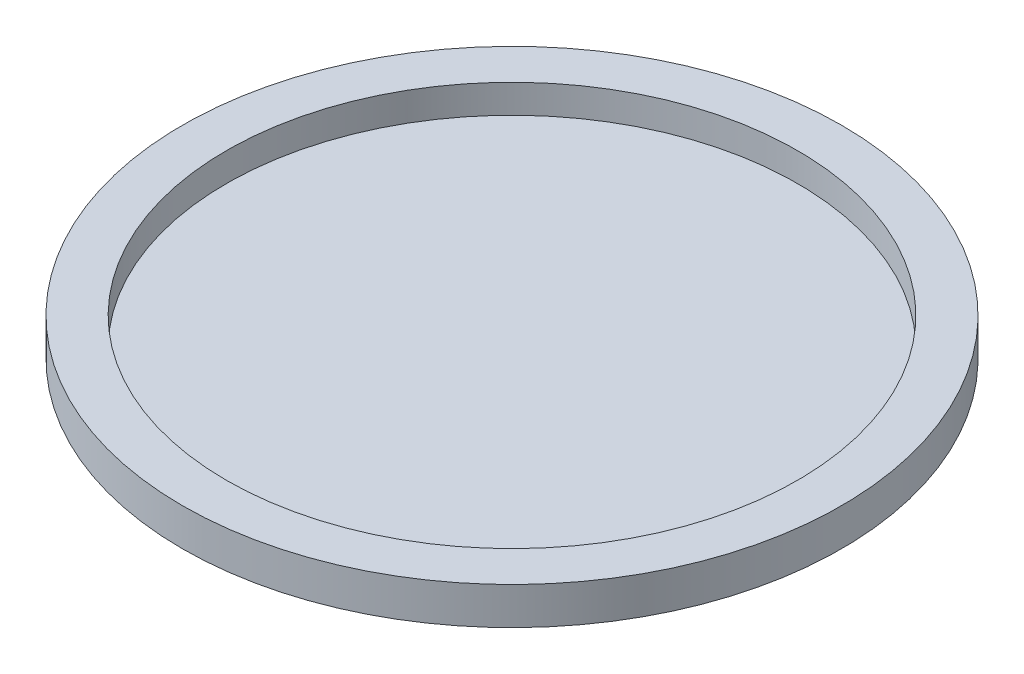
SolidWorks part; units mm, degrees
ref_plane "Спереди" through (0, 0, 0) normal (0, 0, 1) x (1, 0, 0)
ref_plane "Сверху" through (0, 0, 0) normal (0, 1, 0) x (1, 0, 0)
ref_plane "Справа" through (0, 0, 0) normal (1, 0, 0) x (0, 0, -1)
sketch "Эскиз1" plane through (0, 0, 0) normal (0, 1, 0) x (1, 0, 0)
  circle A0 centre (0, 0) radius 15
extrude "Бобышка-Вытянуть1" add sketch "Эскиз1" along normal blind 1.7
sketch "Эскиз2" plane through (0, 0, 0) normal (0, -1, 0) x (1, 0, 0)
  circle A0 centre (0, 0) radius 13.4036
extrude "Бобышка-Вытянуть2" add sketch "Эскиз2" along normal blind 1.2
fillet "Скругление1" radius 1 1 edges at (0, -1.2, -13.4036) type face fillet first side face at (0, -1.2, -13.4036) second side face at (0, -1.2, -13.4036)
sketch "Эскиз4" plane through (0, -1.2, 0) normal (0, -1, 0) x (1, 0, 0)
  circle A0 centre (0, 0) radius 7.1533
extrude "Бобышка-Вытянуть3" add sketch "Эскиз4" along normal blind 2.1
sketch "Эскиз6" plane through (0, 1.7, 0) normal (0, 1, 0) x (1, 0, 0)
  circle A0 centre (0, 0) radius 12.9986
extrude "Вырез-Вытянуть4" cut sketch "Эскиз6" against normal blind 1.3
